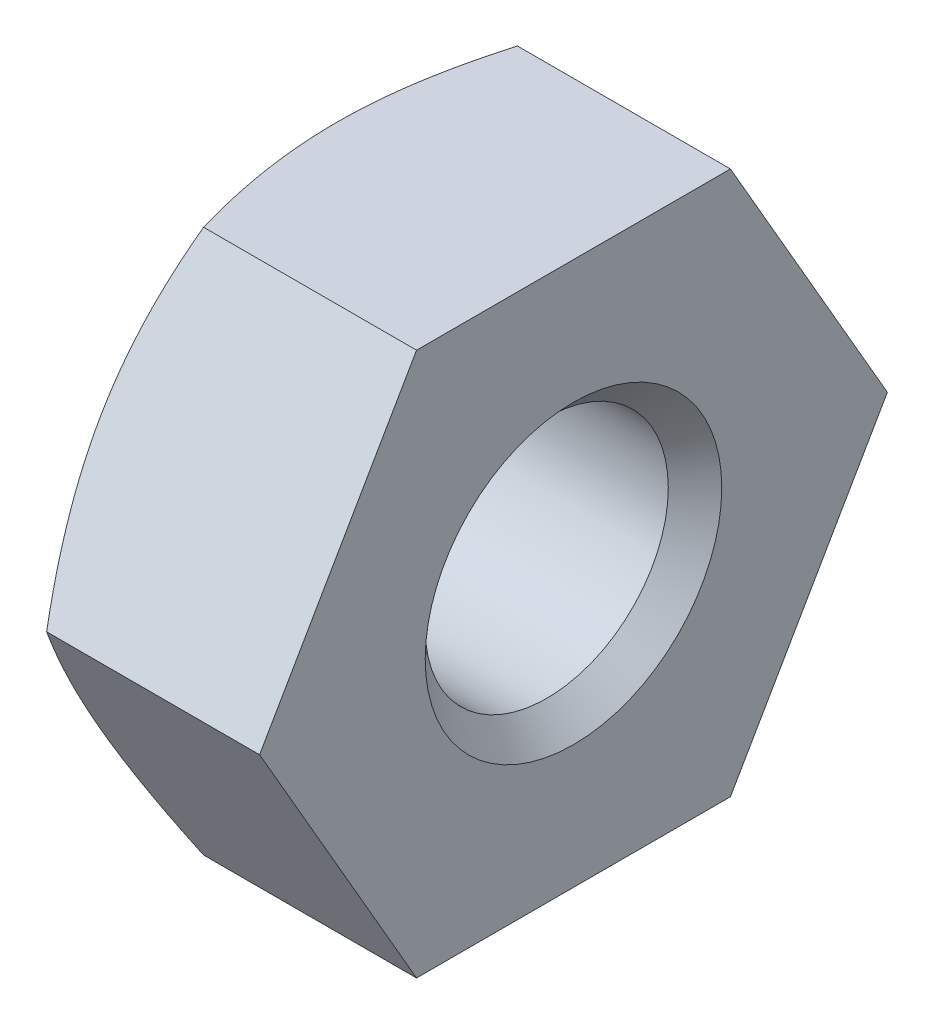
SolidWorks part; units mm, degrees
ref_plane "前视基准面" through (0, 0, 0) normal (0, 0, 1) x (1, 0, 0)
ref_plane "上视基准面" through (0, 0, 0) normal (0, 1, 0) x (1, 0, 0)
ref_plane "右视基准面" through (0, 0, 0) normal (1, 0, 0) x (0, 0, -1)
sketch "草图1" plane through (0, 0, 0) normal (0, 0, 1) x (1, 0, 0)
  line L0 (-1.2, 0) -> (-1.2, 2.75)
  line L1 (-1.2, 2.75) -> (-0.9402, 3.2)
  line L2 (-0.9402, 3.2) -> (1.2, 3.2)
  line L3 (1.2, 3.2) -> (1.2, 0)
  line L4 (1.2, 0) -> (-1.2, 0)
  line L5 (1.2, 0) -> (-1.2, 0) construction
revolve "旋转1" add sketch "草图1" angle 360 about L5 reverse direction yes
sketch "草图2" plane through (0, 0, 0) normal (0, 0, 1) x (1, 0, 0)
  line L0 (-1.2, 0) -> (-1.2, 1.5)
  line L1 (-1.2, 1.5) -> (-0.9295, 1.2295)
  line L2 (-0.9295, 1.2295) -> (0.9295, 1.2295)
  line L3 (0.9295, 1.2295) -> (1.2, 1.5)
  line L4 (1.2, 1.5) -> (1.2, 0)
  line L5 (1.2, 0) -> (-1.2, 0)
  line L6 (1.2, 0) -> (-1.2, 0) construction
revolve "切除-旋转1" cut sketch "草图2" angle 360 about L6 reverse direction yes
cosmetic thread "装饰螺纹线1" parameters "D1"=2.4, "D2"=3
sketch "草图3" plane through (0, 0, 0) normal (1, 0, 0) x (0, 0, -1)
  line L0 (-5.5, 5.5) -> (-5.5, -5.5)
  line L1 (-5.5, -5.5) -> (5.5, -5.5)
  line L2 (5.5, -5.5) -> (5.5, 5.5)
  line L3 (5.5, 5.5) -> (-5.5, 5.5)
  line L4 (-3.1754, 0) -> (-1.5877, -2.75)
  line L5 (-1.5877, -2.75) -> (1.5877, -2.75)
  line L6 (1.5877, -2.75) -> (3.1754, 0)
  line L7 (3.1754, 0) -> (1.5877, 2.75)
  line L8 (1.5877, 2.75) -> (-1.5877, 2.75)
  line L9 (-1.5877, 2.75) -> (-3.1754, 0)
extrude "切除-拉伸1" cut sketch "草图3" along normal blind 1.2 and the other way blind 1.2
ref_plane "C1 XY" through (0, 0, 0) normal (0, 0, 1) x (1, 0, 0)
ref_plane "C1 XZ" through (0, 0, 0) normal (0, -1, 0) x (-1, 0, 0)
ref_plane "C1 YZ" through (1.2, 0, 0) normal (1, 0, 0) x (0, 0, -1)
ref_axis "C1 X" through (-80.9, 0, 0) along (1, 0, 0)
ref_axis "C1 Y" through (1.2, -50, 0) along (0, 1, 0)
ref_axis "C1 Z" through (1.2, 0, 80.9) along (0, 0, -1)
sketch3d "C1"
  point P0 (1.2, 0, 0)
